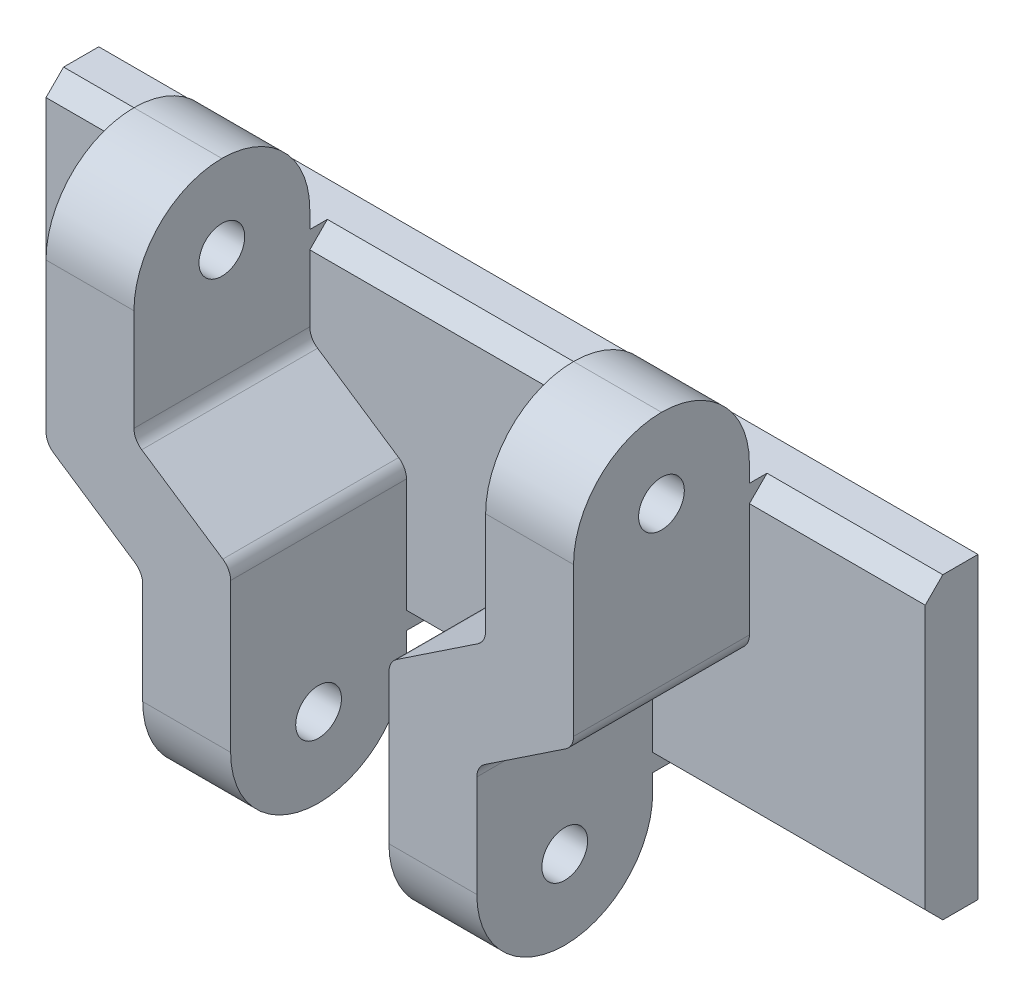
SolidWorks part; units mm, degrees
ref_plane "Plan de face" through (0, 0, 0) normal (0, 0, 1) x (1, 0, 0)
ref_plane "Plan de dessus" through (0, 0, 0) normal (0, 1, 0) x (1, 0, 0)
ref_plane "Plan de droite" through (0, 0, 0) normal (1, 0, 0) x (0, 0, -1)
sketch "Esquisse1" plane through (0, 0, 0) normal (0, 0, 1) x (1, 0, 0)
  line L0 (0, 3.8326) -> (0, 54.1934) construction
  line L1 (0, 0) -> (95.0599, 0) construction
  line L3 (-25, -8.5) -> (25, -8.5)
  line L4 (-25, -8.5) -> (-25, 8.5)
  line L5 (-25, 8.5) -> (25, 8.5)
  line L6 (25, -8.5) -> (25, 8.5)
  line L7 (-25, -8.5) -> (25, 8.5) construction
  line L8 (-25, 8.5) -> (25, -8.5) construction
  dimension "D1" = 17
  dimension "D2" = 50
extrude "Boss.-Extru.1" add sketch "Esquisse1" along normal blind 3
sketch "Esquisse2" plane through (0, 0, 3) normal (0, 0, 1) x (1, 0, 0)
  line L0 (0, 0) -> (0, 17.4412) construction
  line L1 (0, 0) -> (20.6358, 0) construction
  line L2 (-15, 14.5) -> (-15, 0.5)
  line L3 (-15, 0.5) -> (-9.5, -3.1733)
  line L4 (-9.5, -3.1733) -> (-9.5, -14.5)
  line L5 (-9.5, -14.5) -> (-4.5, -14.5)
  line L6 (-4.5, -14.5) -> (-4.5, -0.5)
  line L7 (-4.5, -0.5) -> (-10, 3.1733)
  line L8 (-10, 3.1733) -> (-10, 14.5)
  line L9 (-10, 14.5) -> (-15, 14.5)
  line L10 (-10, -14.5) -> (-15, -14.5) construction
  line L11 (25, 8.5) -> (-25, 8.5) construction
  line L12 (10, -14.5) -> (15, -14.5) construction
  line L13 (0, 0) -> (-20.6358, 0) construction
  line L14 (10, 14.5) -> (15, 14.5)
  line L15 (10, 3.1733) -> (10, 14.5)
  line L16 (4.5, -0.5) -> (10, 3.1733)
  line L17 (4.5, -14.5) -> (4.5, -0.5)
  line L18 (9.5, -14.5) -> (4.5, -14.5)
  line L19 (9.5, -3.1733) -> (9.5, -14.5)
  line L20 (15, 0.5) -> (9.5, -3.1733)
  line L21 (15, 14.5) -> (15, 0.5)
  dimension "D1" = 5
  dimension "D2" = 14.5
  dimension "D3" = 5
  dimension "D4" = 8
  dimension "D5" = 20
  dimension "D6" = 9
extrude "Boss.-Extru.2" add sketch "Esquisse2" along normal blind 10
fillet "Congé1" radius 5 8 edges at (7, -14.5, 13) (7, -14.5, 3) (-7, -14.5, 3) (-7, -14.5, 13) (-12.5, 14.5, 13) (12.5, 14.5, 13) (12.5, 14.5, 3) (-12.5, 14.5, 3)
fillet "Congé2" radius 1 8 edges at (9.5, -3.1733, 8) (10, 3.1733, 8) (-9.5, -3.1733, 8) (-15, 0.5, 8) (4.5, -0.5, 8) (15, 0.5, 8) (-4.5, -0.5, 8) (-10, 3.1733, 8)
chamfer "Chanfrein1" distance 1 angle 45 6 edges at (-17.25, -8.5, 3) (0, -8.5, 3) (17.25, -8.5, 3) (20, 8.5, 3) (-20, 8.5, 3) (0, 8.5, 3)
hole_wizard "Diamètre du perçage Ø2.6 (2.6)1" positions "Esquisse4" profile "Esquisse3" hole size "Ø2.6" standard "Ansi Metric" end condition through all
sketch "Esquisse4" plane through (15, 0, 0) normal (1, 0, 0) x (0, 0, -1)
  line L0 (-8, 10.4555) -> (-8, -9.5445) construction
  line L2 (0, 0) -> (19.6013, 0) construction
  line L4 (7.15, 0) -> (-7.15, 0) construction
  point P58 (-8, -10)
  point P63 (-8, 10)
  dimension "D1" = 20
sketch "Esquisse3" plane through (15, -10, 8) normal (0, 1, 0) x (0, 0, -1)
  line L0 (0, 0) -> (0, 40)
  line L1 (0, 40) -> (1.3, 40)
  line L2 (1.3, 40) -> (1.3, 0)
  line L5 (1.3, 0) -> (0, 0)
  line L11 (0, -6.35) -> (0, 107.95) construction
  dimension "Diamètre du perçage jusqu'au prochain" = 2.6
  dimension "Profondeur du perçage jusqu'au prochain" = 40
